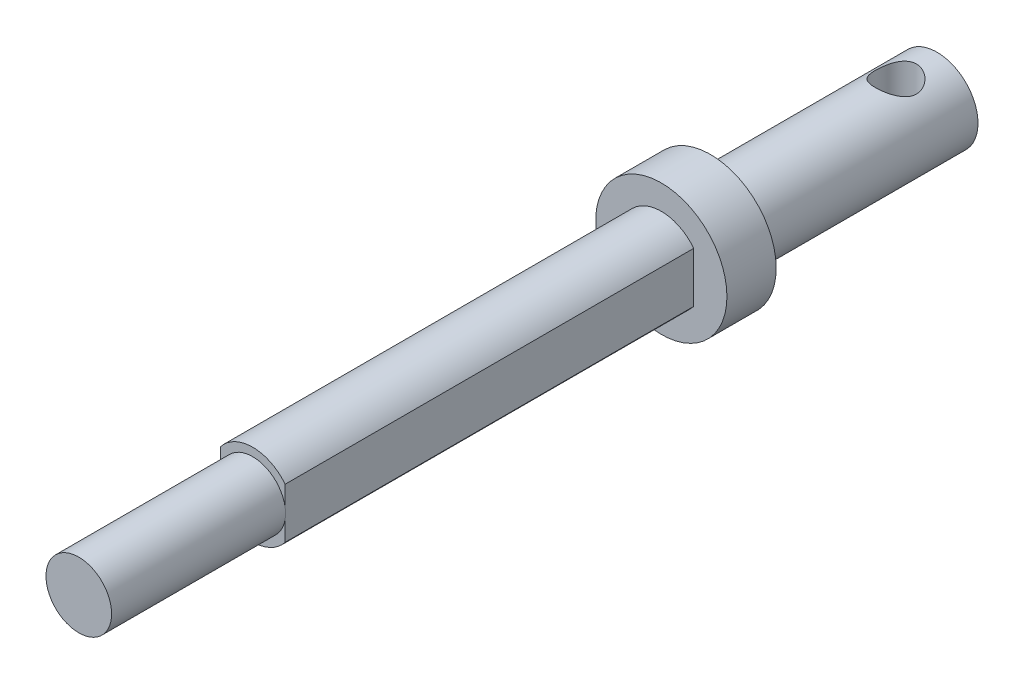
SolidWorks part; units mm, degrees
material "Plain Carbon Steel"
ref_plane "Front Plane" through (0, 0, 0) normal (0, 0, 1) x (1, 0, 0)
ref_plane "Top Plane" through (0, 0, 0) normal (0, 1, 0) x (1, 0, 0)
ref_plane "Right Plane" through (0, 0, 0) normal (1, 0, 0) x (0, 0, -1)
sketch "Sketch1" plane through (0, 0, 0) normal (0, 0, 1) x (1, 0, 0)
  line L0 (1.975, -1.5328) -> (1.975, 1.5328)
  line L1 (-1.975, -1.5328) -> (-1.975, 1.5328)
  line L2 (0, 0) -> (0, -4.6729) construction
  circle A0 centre (0, 0) radius 2.5
  circle A1 centre (0, 0) radius 4
  dimension "D1" = 5
  dimension "D3" = 8
  dimension "D2" = 3.95
extrude "Boss-Extrude1" add sketch "Sketch1" along normal blind 13.8 contours A0
extrude "Boss-Extrude3" add sketch "Sketch1<4>" along normal blind 3 from surface contours A1 starting at face at (2.5, 0, 13.8)
sketch "Sketch1<4>" plane through (0, 0, 0) normal (0, 0, 1) x (1, 0, 0) same geometry as "Sketch1"
extrude "Boss-Extrude2" add sketch "Sketch1<3>" along normal blind 24.9 from surface contours L2 A0 L1 | A0 L2 L0 region at (1.0715, -2.188, 0) starting at face at (4, 0, 16.8)
sketch "Sketch1<3>" plane through (0, 0, 0) normal (0, 0, 1) x (1, 0, 0) same geometry as "Sketch1"
sketch "Sketch2" plane through (0, 0, 41.7) normal (0, 0, 1) x (1, 0, 0)
  circle A0 centre (0, 0) radius 2
  dimension "D1" = 4
extrude "Boss-Extrude4" add sketch "Sketch2" along normal blind 10.6
cosmetic thread "Cosmetic Thread1" parameters "D1"=10.6, "D2"=3.22
sketch "Sketch17" plane through (0, 0, 0) normal (0, 1, 0) x (1, 0, 0)
  line L0 (2.5, 0) -> (-2.5, 0) construction
  circle A0 centre (0, -2.5) radius 1.25
  dimension "D2" = 2.5
  dimension "D1" = 2.5
extrude "Cut-Extrude1" cut sketch "Sketch17" against normal through all both and the other way through all
